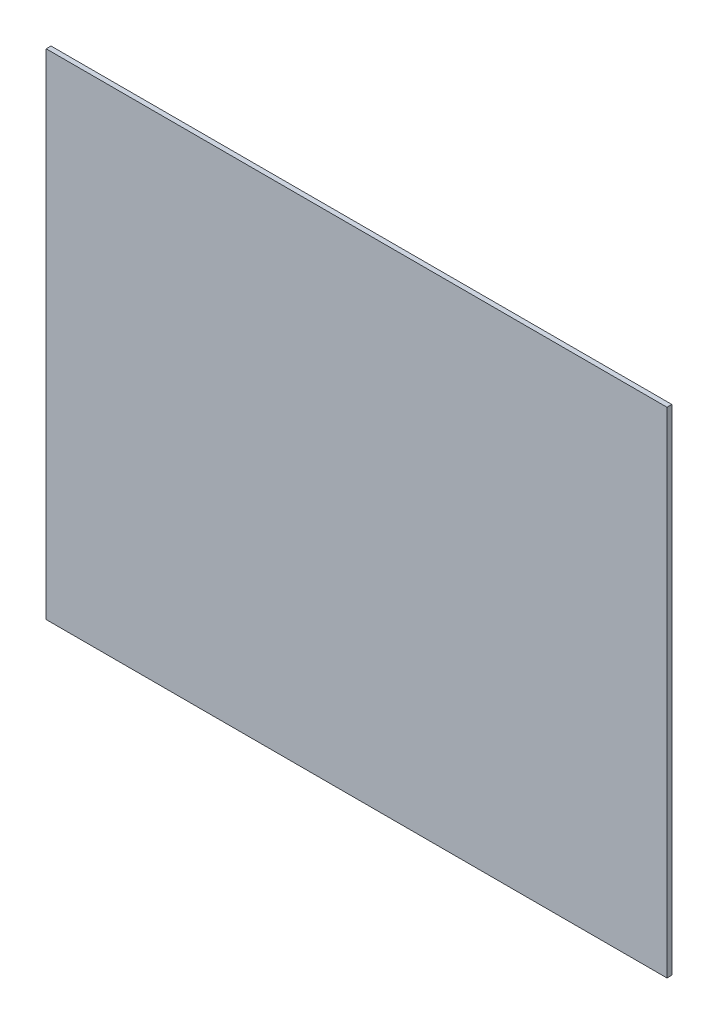
SolidWorks part; units mm, degrees
ref_plane "Plan de face" through (0, 0, 0) normal (0, 0, 1) x (1, 0, 0)
ref_plane "Plan de dessus" through (0, 0, 0) normal (0, 1, 0) x (1, 0, 0)
ref_plane "Plan de droite" through (0, 0, 0) normal (1, 0, 0) x (0, 0, -1)
sketch "Esquisse1" plane through (0, 0, 0) normal (0, 0, 1) x (1, 0, 0)
  line L1 (-416, -331.25) -> (416, -331.25)
  line L2 (-416, -331.25) -> (-416, 331.25)
  line L3 (-416, 331.25) -> (416, 331.25)
  line L4 (416, -331.25) -> (416, 331.25)
  line L5 (-416, -331.25) -> (416, 331.25) construction
  line L6 (-416, 331.25) -> (416, -331.25) construction
  point P0 (0, 0)
  dimension "D1" = 662.5
  dimension "D2" = 832
extrude "Boss.-Extru.1" add sketch "Esquisse1" along normal blind 6.5
ref_axis "Axe1" through (0, 331.25, 0) along (0, -1, 0)
